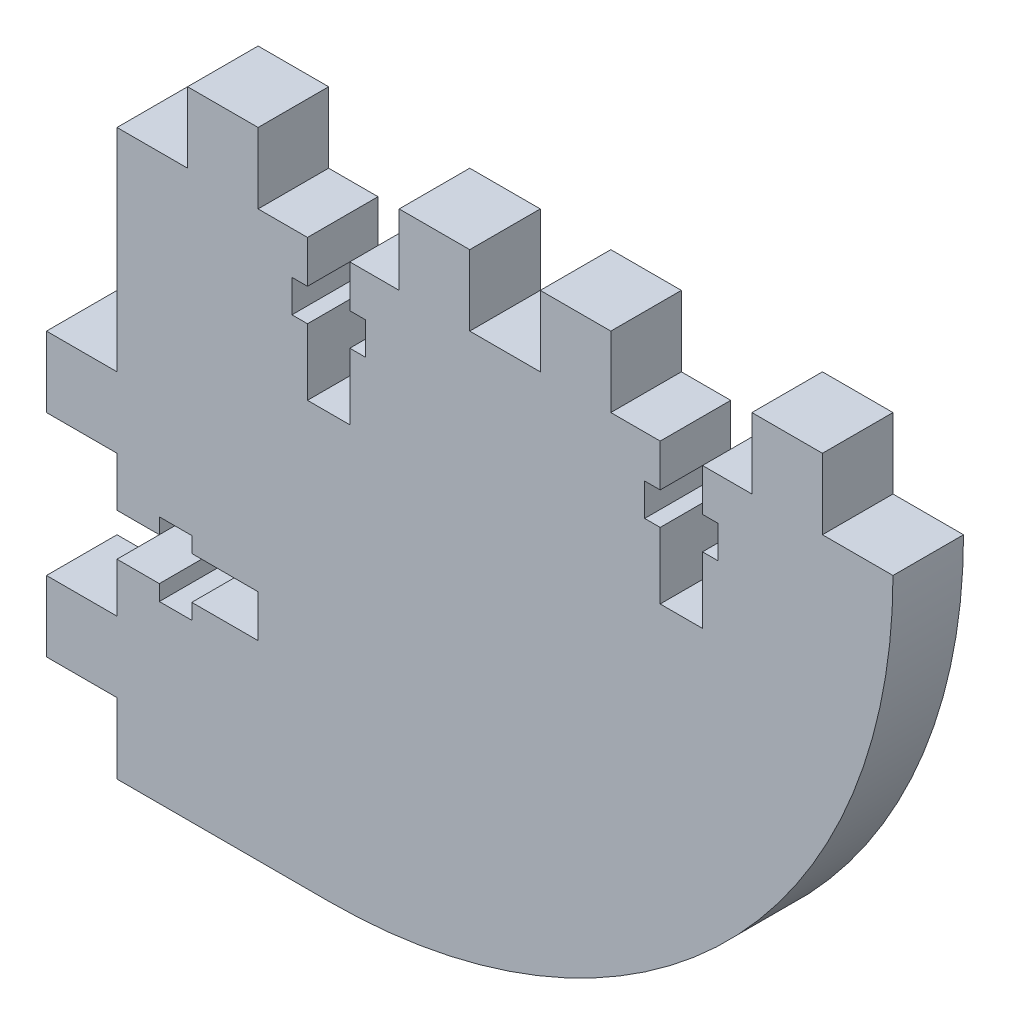
SolidWorks part; units mm, degrees
ref_plane "Plan de face" through (0, 0, 0) normal (0, 0, 1) x (1, 0, 0)
ref_plane "Plan de dessus" through (0, 0, 0) normal (0, 1, 0) x (1, 0, 0)
ref_plane "Plan de droite" through (0, 0, 0) normal (1, 0, 0) x (0, 0, -1)
sketch "Esquisse1" plane through (0, 0, 0) normal (0, 0, 1) x (1, 0, 0)
  line L0 (0, 25) -> (0, 10)
  line L1 (27.5, 4.7921) -> (27.5, -30.9586) construction
  line L5 (25, 25) -> (30, 25)
  line L6 (0, -10) -> (0, -15)
  line L7 (0, -15) -> (55, -15)
  line L8 (55, -15) -> (55, 25)
  line L9 (55, 25) -> (50, 25)
  line L10 (5, 25) -> (0, 25)
  line B0 (3, 2.6) -> (5.3, 2.6)
  line B1 (5.3, -1.5) -> (10, -1.5)
  line B2 (10, 1.5) -> (5.3, 1.5)
  line B3 (5.3, 2.6) -> (5.3, 1.5)
  line B4 (0, 0) -> (11.2208, 0) construction
  line B5 (0, 1.5) -> (0, 5)
  line B6 (-5, 5) -> (-5, 10)
  line B7 (-5, 10) -> (0, 10)
  line B8 (-5, 5) -> (0, 5)
  line B9 (0, -1.5) -> (0, -5)
  line B10 (0, -5) -> (-5, -5)
  line B11 (-5, -5) -> (-5, -10)
  line B12 (-5, -10) -> (0, -10)
  line B13 (0, 1.5) -> (0, -1.5) construction
  line B14 (0, -1.5) -> (3, -1.5)
  line B15 (5.3, -1.5) -> (5.3, -2.6)
  line B16 (3, -2.6) -> (3, -1.5)
  line B17 (10, -1.5) -> (10, 1.5)
  line B18 (3, 1.5) -> (3, 2.6)
  line B19 (5.3, -2.6) -> (3, -2.6)
  line B20 (3, 1.5) -> (0, 1.5)
  line B21 (10, 0) -> (0, 0) construction
  line B22 (42.6, 22) -> (42.6, 19.7)
  line B23 (38.5, 19.7) -> (38.5, 15)
  line B24 (41.5, 15) -> (41.5, 19.7)
  line B25 (42.6, 19.7) -> (41.5, 19.7)
  line B26 (40, 25) -> (40, 13.7792) construction
  line B27 (41.5, 25) -> (45, 25)
  line B28 (45, 30) -> (50, 30)
  line B29 (50, 30) -> (50, 25)
  line B30 (45, 30) -> (45, 25)
  line B31 (38.5, 25) -> (35, 25)
  line B32 (35, 25) -> (35, 30)
  line B33 (35, 30) -> (30, 30)
  line B34 (30, 30) -> (30, 25)
  line B35 (41.5, 25) -> (38.5, 25) construction
  line B36 (38.5, 25) -> (38.5, 22)
  line B37 (38.5, 19.7) -> (37.4, 19.7)
  line B38 (37.4, 22) -> (38.5, 22)
  line B39 (38.5, 15) -> (41.5, 15)
  line B40 (41.5, 22) -> (42.6, 22)
  line B41 (37.4, 19.7) -> (37.4, 22)
  line B42 (41.5, 22) -> (41.5, 25)
  line B43 (40, 15) -> (40, 25) construction
  line B44 (12.4, 22) -> (12.4, 19.7)
  line B45 (16.5, 19.7) -> (16.5, 15)
  line B46 (13.5, 15) -> (13.5, 19.7)
  line B47 (12.4, 19.7) -> (13.5, 19.7)
  line B48 (15, 25) -> (15, 13.7792) construction
  line B49 (13.5, 25) -> (10, 25)
  line B50 (10, 30) -> (5, 30)
  line B51 (5, 30) -> (5, 25)
  line B52 (10, 30) -> (10, 25)
  line B53 (16.5, 25) -> (20, 25)
  line B54 (20, 25) -> (20, 30)
  line B55 (20, 30) -> (25, 30)
  line B56 (25, 30) -> (25, 25)
  line B57 (13.5, 25) -> (16.5, 25) construction
  line B58 (16.5, 25) -> (16.5, 22)
  line B59 (16.5, 19.7) -> (17.6, 19.7)
  line B60 (17.6, 22) -> (16.5, 22)
  line B61 (16.5, 15) -> (13.5, 15)
  line B62 (13.5, 22) -> (12.4, 22)
  line B63 (17.6, 19.7) -> (17.6, 22)
  line B64 (13.5, 22) -> (13.5, 25)
  line B65 (15, 15) -> (15, 25) construction
  dimension "D1" = 5
  dimension "D3" = 5
  dimension "D4" = 25
sketch_block_instance "Insert M3 plots ep 5mm-1"
sketch_block "Insert M3 plots ep 5mm" parameters "D1"=10, "D2"=5, "D3"=5
sketch_block_instance "Decoupe Insert M3-4"
sketch_block "Decoupe Insert M3" parameters "D1"=5.2, "D2"=3, "D3"=2.3, "D4"=3, "D5"=10
sketch_block_instance "Insert M3 plots ep 5mm-3"
sketch_block_instance "Insert M3 plots ep 5mm-4"
extrude "Boss.-Extru.1" add sketch "Esquisse1" along normal blind 5 contours B42 B40 B22 B25 B24 B39 B23 B37 B41 B38 B36 B31 B32 B33 B34 B7 B6 B8 B5 B20 B18 B0 B3 B2 B17 B1 B15 B19 B16 B14 B9 B10 B11 B12 L6 L7 L8 L9 B29 B28 B30 B27 region at (27.1851, 5.4967, 0)
fillet "Congé1" radius 40 1 edges at (55, -15, 2.5)
